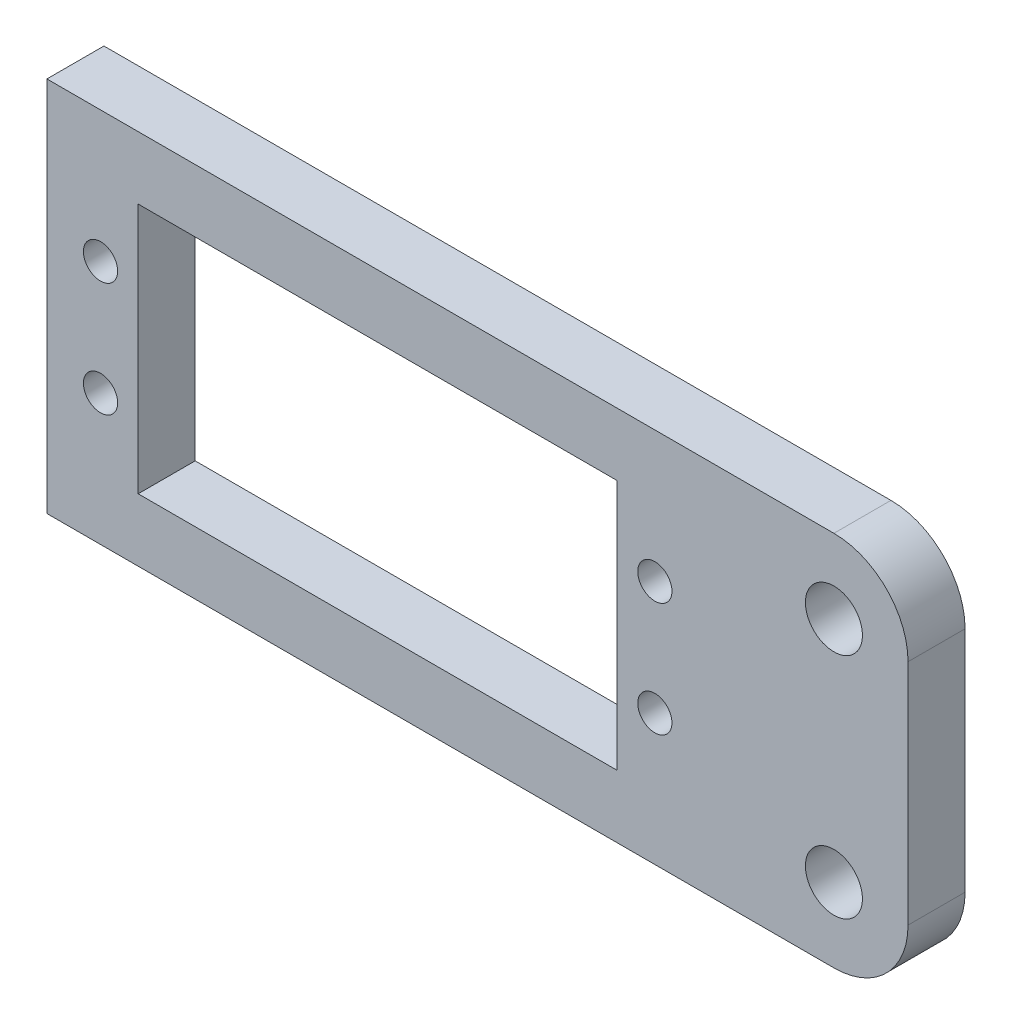
SolidWorks part; units mm, degrees
ref_plane "Front Plane" through (0, 0, 0) normal (0, 0, 1) x (1, 0, 0)
ref_plane "Top Plane" through (0, 0, 0) normal (0, 1, 0) x (1, 0, 0)
ref_plane "Right Plane" through (0, 0, 0) normal (1, 0, 0) x (0, 0, -1)
ref_axis "X" through (-88.99, 0, 0) along (1, 0, 0)
ref_axis "Y" through (0, 55, 0) along (0, -1, 0)
ref_axis "Z" through (0, 0, -88.99) along (0, 0, 1)
sketch "Sketch1" plane through (0, 0, 0) normal (0, 0, 1) x (1, 0, 0)
  line L0 (40, -10) -> (40, 10) construction
  line L1 (0, 0) -> (40, 0) construction
  line L2 (24.3, 5) -> (24.3, -5) construction
  line L3 (-21, 11) -> (21, 11)
  line L4 (-21, 11) -> (-21, -11)
  line L5 (-21, -11) -> (21, -11)
  line L6 (21, 11) -> (21, -11)
  line L7 (-21, 11) -> (21, -11) construction
  line L8 (-21, -11) -> (21, 11) construction
  line L9 (0, 0) -> (0, 11) construction
  line L10 (40, -16.5) -> (-29, -16.5)
  line L11 (-29, -16.5) -> (-29, 16.5)
  line L12 (-29, 16.5) -> (40, 16.5)
  line L13 (46.5, 10) -> (46.5, -10)
  line L14 (40, 0) -> (46.5, 0) construction
  circle A0 centre (40, -10) radius 2.5
  circle A1 centre (40, 10) radius 2.5
  circle A2 centre (24.3, 5) radius 1.5
  circle A3 centre (24.3, -5) radius 1.5
  circle A4 centre (-24.3, -5) radius 1.5
  circle A5 centre (-24.3, 5) radius 1.5
  arc A6 (40, 16.5) -> (46.5, 10) centre (40, 10) cw
  arc A7 (46.5, -10) -> (40, -16.5) centre (40, -10) cw
  point P14 (24.3, 0)
  point P23 (0, 0)
  dimension "D1" = 22
  dimension "D4" = 5
  dimension "D6" = 3
  dimension "D7" = 24.3
  dimension "D10" = 4
  dimension "D2" = 42
  dimension "D3" = 40
  dimension "D5" = 20
  dimension "D8" = 10
  dimension "D9" = 10
  dimension "D11" = 8
extrude "Boss-Extrude1" add sketch "Sketch1" against normal blind 5
